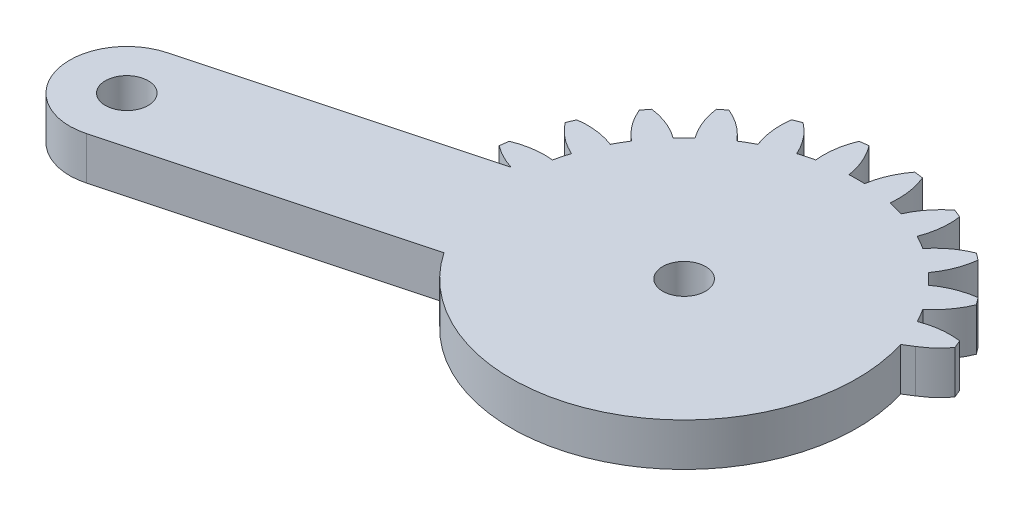
SolidWorks part; units mm, degrees
ref_plane "Front Plane" through (0, 0, 0) normal (0, 0, 1) x (1, 0, 0)
ref_plane "Top Plane" through (0, 0, 0) normal (0, 1, 0) x (1, 0, 0)
ref_plane "Right Plane" through (0, 0, 0) normal (1, 0, 0) x (0, 0, -1)
sketch "Sketch1" plane through (0, 0, 0) normal (0, 1, 0) x (1, 0, 0)
  line L0 (20.6437, 4) -> (2.0816, 4)
  line L1 (2.0816, -4) -> (20.6437, -4)
  arc A0 (2.0816, 4) -> (3.5217, 5.3071) centre (-0.7683, 8.5867) ccw
  arc A1 (3.5217, 5.3071) -> (3.2829, 5.8838) centre (-10.1063, 0) ccw
  arc A2 (3.2829, 5.8838) -> (0.6271, 5.5703) centre (2.5684, 0.5313) ccw
  arc A3 (0.6271, 5.5703) -> (0.0844, 6.5103) centre (-10.1063, 0) ccw
  arc A4 (0.0844, 6.5103) -> (1.6838, 8.6535) centre (-3.3089, 10.711) ccw
  arc A5 (1.6838, 8.6535) -> (1.3038, 9.1487) centre (-10.1063, 0) ccw
  arc A6 (1.3038, 9.1487) -> (-1.1803, 8.1585) centre (1.999, 3.7936) ccw
  arc A7 (-1.1803, 8.1585) -> (-1.9479, 8.926) centre (-10.1063, 0) ccw
  arc A8 (-1.9479, 8.926) -> (-0.9576, 11.4102) centre (-6.3127, 12.1053) ccw
  arc A9 (-0.9576, 11.4102) -> (-1.4528, 11.7901) centre (-10.1063, 0) ccw
  arc A10 (-1.4528, 11.7901) -> (-3.596, 10.1907) centre (0.6046, 6.7975) ccw
  arc A11 (-3.596, 10.1907) -> (-4.5361, 10.7334) centre (-10.1063, 0) ccw
  arc A12 (-4.5361, 10.7334) -> (-4.2225, 13.3892) centre (-9.5751, 12.6747) ccw
  arc A13 (-4.2225, 13.3892) -> (-4.7992, 13.6281) centre (-10.1063, 0) ccw
  arc A14 (-4.7992, 13.6281) -> (-6.4554, 11.5285) centre (-1.5196, 9.3381) ccw
  arc A15 (-6.4554, 11.5285) -> (-7.5039, 11.8094) centre (-10.1063, 0) ccw
  arc A16 (-7.5039, 11.8094) -> (-7.8884, 14.4558) centre (-12.8736, 12.3803) ccw
  arc A17 (-7.8884, 14.4558) -> (-8.5072, 14.5373) centre (-10.1063, 0) ccw
  arc A18 (-8.5072, 14.5373) -> (-9.5636, 12.0806) centre (-4.2291, 11.2423) ccw
  arc A19 (-9.5636, 12.0806) -> (-10.6491, 12.0806) centre (-10.1063, 0) ccw
  arc A20 (-10.6491, 12.0806) -> (-11.7054, 14.5373) centre (-15.9836, 11.2423) ccw
  arc A21 (-11.7054, 14.5373) -> (-12.3243, 14.4558) centre (-10.1063, 0) ccw
  arc A22 (-12.3243, 14.4558) -> (-12.7088, 11.8094) centre (-7.3391, 12.3803) ccw
  arc A23 (-12.7088, 11.8094) -> (-13.7573, 11.5285) centre (-10.1063, 0) ccw
  arc A24 (-13.7573, 11.5285) -> (-15.4135, 13.6281) centre (-18.6931, 9.3381) ccw
  arc A25 (-15.4135, 13.6281) -> (-15.9901, 13.3892) centre (-10.1063, 0) ccw
  arc A26 (-15.9901, 13.3892) -> (-15.6766, 10.7334) centre (-10.6376, 12.6747) ccw
  arc A27 (-15.6766, 10.7334) -> (-16.6166, 10.1907) centre (-10.1063, 0) ccw
  arc A28 (-16.6166, 10.1907) -> (-18.7599, 11.7901) centre (-20.8173, 6.7975) ccw
  arc A29 (-18.7599, 11.7901) -> (-19.255, 11.4102) centre (-10.1063, 0) ccw
  arc A30 (-19.255, 11.4102) -> (-18.2648, 8.926) centre (-13.9, 12.1053) ccw
  arc A31 (-18.2648, 8.926) -> (-19.0324, 8.1585) centre (-10.1063, 0) ccw
  arc A32 (-19.0324, 8.1585) -> (-21.5165, 9.1487) centre (-22.2117, 3.7936) ccw
  arc A33 (-21.5165, 9.1487) -> (-21.8965, 8.6535) centre (-10.1063, 0) ccw
  arc A34 (-21.8965, 8.6535) -> (-20.2971, 6.5103) centre (-16.9038, 10.711) ccw
  arc A35 (-20.2971, 6.5103) -> (-20.8398, 5.5703) centre (-10.1063, 0) ccw
  arc A36 (-20.8398, 5.5703) -> (-23.4956, 5.8838) centre (-22.7811, 0.5313) ccw
  arc A37 (-23.4956, 5.8838) -> (-23.7344, 5.3071) centre (-10.1063, 0) ccw
  arc A38 (-23.7344, 5.3071) -> (-21.6348, 3.6509) centre (-19.4444, 8.5867) ccw
  arc A39 (-21.6348, 3.6509) -> (-21.9157, 2.6025) centre (-10.1063, 0) ccw
  arc A40 (-21.9157, 2.6025) -> (-24.5622, 2.2179) centre (-22.4867, -2.7673) ccw
  arc A41 (-24.5622, 2.2179) -> (-24.6437, 1.5991) centre (-10.1063, 0) ccw
  arc A42 (-24.6437, 1.5991) -> (-22.1869, 0.5427) centre (-21.3486, 5.8773) ccw
  arc A43 (-22.1869, 0.5427) -> (-22.1869, -0.5427) centre (-10.1063, 0) ccw
  arc A44 (-22.1869, -0.5427) -> (-24.6437, -1.5991) centre (-21.3486, -5.8773) ccw
  arc A45 (-24.6437, -1.5991) -> (-24.5622, -2.2179) centre (-10.1063, 0) ccw
  arc A46 (-24.5622, -2.2179) -> (-21.9157, -2.6025) centre (-22.4867, 2.7673) ccw
  arc A47 (-21.9157, -2.6025) -> (-21.6348, -3.6509) centre (-10.1063, 0) ccw
  arc A48 (-21.6348, -3.6509) -> (-23.7344, -5.3071) centre (-19.4444, -8.5867) ccw
  arc A49 (-23.7344, -5.3071) -> (-23.4956, -5.8838) centre (-10.1063, 0) ccw
  arc A50 (-23.4956, -5.8838) -> (-20.8398, -5.5703) centre (-22.7811, -0.5313) ccw
  arc A51 (-20.8398, -5.5703) -> (-20.2971, -6.5103) centre (-10.1063, 0) ccw
  arc A52 (-20.2971, -6.5103) -> (-21.8965, -8.6535) centre (-16.9038, -10.711) ccw
  arc A53 (-21.8965, -8.6535) -> (-21.5165, -9.1487) centre (-10.1063, 0) ccw
  arc A54 (-21.5165, -9.1487) -> (-19.0324, -8.1585) centre (-22.2117, -3.7936) ccw
  arc A55 (-19.0324, -8.1585) -> (-18.2648, -8.926) centre (-10.1063, 0) ccw
  arc A56 (-18.2648, -8.926) -> (-19.255, -11.4102) centre (-13.9, -12.1053) ccw
  arc A57 (-19.255, -11.4102) -> (-18.7599, -11.7901) centre (-10.1063, 0) ccw
  arc A58 (-18.7599, -11.7901) -> (-16.6166, -10.1907) centre (-20.8173, -6.7975) ccw
  arc A59 (-16.6166, -10.1907) -> (-15.6766, -10.7334) centre (-10.1063, 0) ccw
  arc A60 (-15.6766, -10.7334) -> (-15.9901, -13.3892) centre (-10.6376, -12.6747) ccw
  arc A61 (-15.9901, -13.3892) -> (-15.4135, -13.6281) centre (-10.1063, 0) ccw
  arc A62 (-15.4135, -13.6281) -> (-13.7573, -11.5285) centre (-18.6931, -9.3381) ccw
  arc A63 (-13.7573, -11.5285) -> (-12.7088, -11.8094) centre (-10.1063, 0) ccw
  arc A64 (-12.7088, -11.8094) -> (-12.3243, -14.4558) centre (-7.3391, -12.3803) ccw
  arc A65 (-12.3243, -14.4558) -> (-11.7054, -14.5373) centre (-10.1063, 0) ccw
  arc A66 (-11.7054, -14.5373) -> (-10.6491, -12.0806) centre (-15.9836, -11.2423) ccw
  arc A67 (-10.6491, -12.0806) -> (-9.5636, -12.0806) centre (-10.1063, 0) ccw
  arc A68 (-9.5636, -12.0806) -> (-8.5072, -14.5373) centre (-4.2291, -11.2423) ccw
  arc A69 (-8.5072, -14.5373) -> (-7.8884, -14.4558) centre (-10.1063, 0) ccw
  arc A70 (-7.8884, -14.4558) -> (-7.5039, -11.8094) centre (-12.8736, -12.3803) ccw
  arc A71 (-7.5039, -11.8094) -> (-6.4554, -11.5285) centre (-10.1063, 0) ccw
  arc A72 (-6.4554, -11.5285) -> (-4.7992, -13.6281) centre (-1.5196, -9.3381) ccw
  arc A73 (-4.7992, -13.6281) -> (-4.2225, -13.3892) centre (-10.1063, 0) ccw
  arc A74 (-4.2225, -13.3892) -> (-4.5361, -10.7334) centre (-9.5751, -12.6747) ccw
  arc A75 (-4.5361, -10.7334) -> (-3.596, -10.1907) centre (-10.1063, 0) ccw
  arc A76 (-3.596, -10.1907) -> (-1.4528, -11.7901) centre (0.6046, -6.7975) ccw
  arc A77 (-1.4528, -11.7901) -> (-0.9576, -11.4102) centre (-10.1063, 0) ccw
  arc A78 (-0.9576, -11.4102) -> (-1.9479, -8.926) centre (-6.3127, -12.1053) ccw
  arc A79 (-1.9479, -8.926) -> (-1.1803, -8.1585) centre (-10.1063, 0) ccw
  arc A80 (-1.1803, -8.1585) -> (1.3038, -9.1487) centre (1.999, -3.7936) ccw
  arc A81 (1.3038, -9.1487) -> (1.6838, -8.6535) centre (-10.1063, 0) ccw
  arc A82 (1.6838, -8.6535) -> (0.0844, -6.5103) centre (-3.3089, -10.711) ccw
  arc A83 (0.0844, -6.5103) -> (0.6271, -5.5703) centre (-10.1063, 0) ccw
  arc A84 (0.6271, -5.5703) -> (3.2829, -5.8838) centre (2.5684, -0.5313) ccw
  arc A85 (3.2829, -5.8838) -> (3.5217, -5.3071) centre (-10.1063, 0) ccw
  arc A86 (3.5217, -5.3071) -> (2.0816, -4) centre (-0.7683, -8.5867) ccw
  arc A87 (20.6437, -4) -> (20.6437, 4) centre (20.6437, 0) ccw
  circle A88 centre (-10.1063, 0) radius 1.5
  circle A89 centre (20.6437, 0) radius 1.5
  dimension "D1" = 3
  dimension "D2" = 3
extrude "Boss-Extrude1" add sketch "Sketch1" along normal blind 3
sketch "Sketch3" plane through (0, 3, 0) normal (0, 1, 0) x (1, 0, 0)
  line L0 (-10.1063, 0) -> (-40.8563, 0) construction
  line L1 (-10.1063, 0) -> (-40.8563, -8.2394)
  line L2 (-11.1416, 3.8637) -> (-41.8916, -4.3757)
  line L3 (-9.0711, -3.8637) -> (-39.8211, -12.1031)
  circle A0 centre (-10.1063, 0) radius 1.5
  circle A1 centre (20.6437, 0) radius 1.5 construction
  circle A2 centre (20.6437, 0) radius 1.5
  circle A3 centre (-40.8563, -8.2394) radius 1.5
  circle A4 centre (-40.8563, -8.2394) radius 4
  circle A5 centre (-10.1063, 0) radius 4
  dimension "D2" = 3
  dimension "D5" = 3
  dimension "D6" = 8
  dimension "D7" = 8
  dimension "D1" = 30.75
  dimension "D3" = 30.75
  dimension "D4" = 15
extrude "Boss-Extrude2" add sketch "Sketch3" against normal blind 3 contours L0 A5 L2 | A5 L0 L2 A4 L1 | A4 A3 | A5 L1 A4 L3 | L0 A0 L1 A5 | A0 L0 A5 L1 region at (-13.0123, 3, 0.3826) region at (-12.8563, 3, -0.1131) region at (-28.0097, 3, 2.8847) region at (-17.5095, 3, -1.168) region at (-24.9445, 3, 6.1234) region at (-37.0027, 3, 7.7321)
sketch "Sketch4" plane through (0, 3, 0) normal (0, 1, 0) x (1, 0, 0)
  line L0 (20.6437, 4) -> (2.0816, 4) construction
  line L1 (2.0816, -4) -> (20.6437, -4) construction
  line L2 (20.6437, 4) -> (2.0816, 4)
  line L3 (2.0816, -4) -> (20.6437, -4)
  line L4 (2.0816, 4) -> (1.4381, 3.6001)
  line L5 (-20.8438, -7.0182) -> (-20.0942, -6.8174)
  line L8 (-22.9143, 0.7092) -> (-41.8916, -4.3757)
  line L9 (-39.8211, -12.1031) -> (-20.8438, -7.0182)
  line L10 (2.0816, -4) -> (20.6437, -4)
  line L11 (20.6437, 4) -> (2.0816, 4)
  line L12 (-22.9143, 0.7092) -> (-41.8916, -4.3757)
  line L13 (-39.8211, -12.1031) -> (-20.8438, -7.0182)
  line L14 (2.0816, -4) -> (20.6437, -4)
  line L15 (20.6437, 4) -> (2.0816, 4)
  circle A0 centre (-10.1063, 0) radius 12.0927
  arc A1 (3.2829, 5.8838) -> (0.6271, 5.5703) centre (2.5684, 0.5313) ccw construction
  arc A2 (3.5217, 5.3071) -> (3.2829, 5.8838) centre (-10.1063, 0) ccw construction
  arc A3 (2.0816, 4) -> (3.5217, 5.3071) centre (-0.7683, 8.5867) ccw construction
  arc A4 (20.6437, -4) -> (20.6437, 4) centre (20.6437, 0) ccw construction
  arc A5 (3.5217, -5.3071) -> (2.0816, -4) centre (-0.7683, -8.5867) ccw construction
  arc A6 (3.2829, -5.8838) -> (3.5217, -5.3071) centre (-10.1063, 0) ccw construction
  arc A7 (0.6271, -5.5703) -> (3.2829, -5.8838) centre (2.5684, -0.5313) ccw construction
  arc A8 (3.2829, 5.8838) -> (0.6271, 5.5703) centre (2.5684, 0.5313) ccw
  arc A9 (3.5217, 5.3071) -> (3.2829, 5.8838) centre (-10.1063, 0) ccw
  arc A10 (2.0816, 4) -> (3.5217, 5.3071) centre (-0.7683, 8.5867) ccw
  arc A11 (20.6437, -4) -> (20.6437, 4) centre (20.6437, 0) ccw
  arc A12 (3.5217, -5.3071) -> (2.0816, -4) centre (-0.7683, -8.5867) ccw
  arc A13 (3.2829, -5.8838) -> (3.5217, -5.3071) centre (-10.1063, 0) ccw
  arc A14 (0.6271, -5.5703) -> (3.2829, -5.8838) centre (2.5684, -0.5313) ccw
  arc A95 (-24.6437, 1.5991) -> (-22.9143, 0.7092) centre (-21.3486, 5.8773) ccw
  arc A96 (-41.8916, -4.3757) -> (-39.8211, -12.1031) centre (-40.8563, -8.2394) ccw
  arc A97 (-20.8438, -7.0182) -> (-21.8965, -8.6535) centre (-16.9038, -10.711) ccw
  arc A98 (-21.8965, -8.6535) -> (-21.5165, -9.1487) centre (-10.1063, 0) ccw
  arc A99 (-21.5165, -9.1487) -> (-19.0324, -8.1585) centre (-22.2117, -3.7936) ccw
  arc A100 (-19.0324, -8.1585) -> (-18.2648, -8.926) centre (-10.1063, 0) ccw
  arc A101 (-18.2648, -8.926) -> (-19.255, -11.4102) centre (-13.9, -12.1053) ccw
  arc A102 (-19.255, -11.4102) -> (-18.7599, -11.7901) centre (-10.1063, 0) ccw
  arc A103 (-18.7599, -11.7901) -> (-16.6166, -10.1907) centre (-20.8173, -6.7975) ccw
  arc A104 (-16.6166, -10.1907) -> (-15.6766, -10.7334) centre (-10.1063, 0) ccw
  arc A105 (-15.6766, -10.7334) -> (-15.9901, -13.3892) centre (-10.6376, -12.6747) ccw
  arc A106 (-15.9901, -13.3892) -> (-15.4135, -13.6281) centre (-10.1063, 0) ccw
  arc A107 (-15.4135, -13.6281) -> (-13.7573, -11.5285) centre (-18.6931, -9.3381) ccw
  arc A108 (-13.7573, -11.5285) -> (-12.7088, -11.8094) centre (-10.1063, 0) ccw
  arc A109 (-12.7088, -11.8094) -> (-12.3243, -14.4558) centre (-7.3391, -12.3803) ccw
  arc A110 (-12.3243, -14.4558) -> (-11.7054, -14.5373) centre (-10.1063, 0) ccw
  arc A111 (-11.7054, -14.5373) -> (-10.6491, -12.0806) centre (-15.9836, -11.2423) ccw
  arc A112 (-10.6491, -12.0806) -> (-9.5636, -12.0806) centre (-10.1063, 0) ccw
  arc A113 (-9.5636, -12.0806) -> (-8.5072, -14.5373) centre (-4.2291, -11.2423) ccw
  arc A114 (-8.5072, -14.5373) -> (-7.8884, -14.4558) centre (-10.1063, 0) ccw
  arc A115 (-7.8884, -14.4558) -> (-7.5039, -11.8094) centre (-12.8736, -12.3803) ccw
  arc A116 (-7.5039, -11.8094) -> (-6.4554, -11.5285) centre (-10.1063, 0) ccw
  arc A117 (-6.4554, -11.5285) -> (-4.7992, -13.6281) centre (-1.5196, -9.3381) ccw
  arc A118 (-4.7992, -13.6281) -> (-4.2225, -13.3892) centre (-10.1063, 0) ccw
  arc A119 (-4.2225, -13.3892) -> (-4.5361, -10.7334) centre (-9.5751, -12.6747) ccw
  arc A120 (-4.5361, -10.7334) -> (-3.596, -10.1907) centre (-10.1063, 0) ccw
  arc A121 (-3.596, -10.1907) -> (-1.4528, -11.7901) centre (0.6046, -6.7975) ccw
  arc A122 (-1.4528, -11.7901) -> (-0.9576, -11.4102) centre (-10.1063, 0) ccw
  arc A123 (-0.9576, -11.4102) -> (-1.9479, -8.926) centre (-6.3127, -12.1053) ccw
  arc A124 (-1.9479, -8.926) -> (-1.1803, -8.1585) centre (-10.1063, 0) ccw
  arc A125 (-1.1803, -8.1585) -> (1.3038, -9.1487) centre (1.999, -3.7936) ccw
  arc A126 (1.3038, -9.1487) -> (1.6838, -8.6535) centre (-10.1063, 0) ccw
  arc A127 (1.6838, -8.6535) -> (0.0844, -6.5103) centre (-3.3089, -10.711) ccw
  arc A128 (0.0844, -6.5103) -> (0.6271, -5.5703) centre (-10.1063, 0) ccw
  arc A129 (0.6271, -5.5703) -> (3.2829, -5.8838) centre (2.5684, -0.5313) ccw
  arc A130 (3.2829, -5.8838) -> (3.5217, -5.3071) centre (-10.1063, 0) ccw
  arc A131 (3.5217, -5.3071) -> (2.0816, -4) centre (-0.7683, -8.5867) ccw
  arc A132 (20.6437, -4) -> (20.6437, 4) centre (20.6437, 0) ccw
  arc A133 (2.0816, 4) -> (3.5217, 5.3071) centre (-0.7683, 8.5867) ccw
  arc A134 (3.5217, 5.3071) -> (3.2829, 5.8838) centre (-10.1063, 0) ccw
  arc A135 (3.2829, 5.8838) -> (0.6271, 5.5703) centre (2.5684, 0.5313) ccw
  arc A136 (0.6271, 5.5703) -> (0.0844, 6.5103) centre (-10.1063, 0) ccw
  arc A137 (0.0844, 6.5103) -> (1.6838, 8.6535) centre (-3.3089, 10.711) ccw
  arc A138 (1.6838, 8.6535) -> (1.3038, 9.1487) centre (-10.1063, 0) ccw
  arc A139 (1.3038, 9.1487) -> (-1.1803, 8.1585) centre (1.999, 3.7936) ccw
  arc A140 (-1.1803, 8.1585) -> (-1.9479, 8.926) centre (-10.1063, 0) ccw
  arc A141 (-1.9479, 8.926) -> (-0.9576, 11.4102) centre (-6.3127, 12.1053) ccw
  arc A142 (-0.9576, 11.4102) -> (-1.4528, 11.7901) centre (-10.1063, 0) ccw
  arc A143 (-1.4528, 11.7901) -> (-3.596, 10.1907) centre (0.6046, 6.7975) ccw
  arc A144 (-3.596, 10.1907) -> (-4.5361, 10.7334) centre (-10.1063, 0) ccw
  arc A145 (-4.5361, 10.7334) -> (-4.2225, 13.3892) centre (-9.5751, 12.6747) ccw
  arc A146 (-4.2225, 13.3892) -> (-4.7992, 13.6281) centre (-10.1063, 0) ccw
  arc A147 (-4.7992, 13.6281) -> (-6.4554, 11.5285) centre (-1.5196, 9.3381) ccw
  arc A148 (-6.4554, 11.5285) -> (-7.5039, 11.8094) centre (-10.1063, 0) ccw
  arc A149 (-7.5039, 11.8094) -> (-7.8884, 14.4558) centre (-12.8736, 12.3803) ccw
  arc A150 (-7.8884, 14.4558) -> (-8.5072, 14.5373) centre (-10.1063, 0) ccw
  arc A151 (-8.5072, 14.5373) -> (-9.5636, 12.0806) centre (-4.2291, 11.2423) ccw
  arc A152 (-9.5636, 12.0806) -> (-10.6491, 12.0806) centre (-10.1063, 0) ccw
  arc A153 (-10.6491, 12.0806) -> (-11.7054, 14.5373) centre (-15.9836, 11.2423) ccw
  arc A154 (-11.7054, 14.5373) -> (-12.3243, 14.4558) centre (-10.1063, 0) ccw
  arc A155 (-12.3243, 14.4558) -> (-12.7088, 11.8094) centre (-7.3391, 12.3803) ccw
  arc A156 (-12.7088, 11.8094) -> (-13.7573, 11.5285) centre (-10.1063, 0) ccw
  arc A157 (-13.7573, 11.5285) -> (-15.4135, 13.6281) centre (-18.6931, 9.3381) ccw
  arc A158 (-15.4135, 13.6281) -> (-15.9901, 13.3892) centre (-10.1063, 0) ccw
  arc A159 (-15.9901, 13.3892) -> (-15.6766, 10.7334) centre (-10.6376, 12.6747) ccw
  arc A160 (-15.6766, 10.7334) -> (-16.6166, 10.1907) centre (-10.1063, 0) ccw
  arc A161 (-16.6166, 10.1907) -> (-18.7599, 11.7901) centre (-20.8173, 6.7975) ccw
  arc A162 (-18.7599, 11.7901) -> (-19.255, 11.4102) centre (-10.1063, 0) ccw
  arc A163 (-19.255, 11.4102) -> (-18.2648, 8.926) centre (-13.9, 12.1053) ccw
  arc A164 (-18.2648, 8.926) -> (-19.0324, 8.1585) centre (-10.1063, 0) ccw
  arc A165 (-19.0324, 8.1585) -> (-21.5165, 9.1487) centre (-22.2117, 3.7936) ccw
  arc A166 (-21.5165, 9.1487) -> (-21.8965, 8.6535) centre (-10.1063, 0) ccw
  arc A167 (-21.8965, 8.6535) -> (-20.2971, 6.5103) centre (-16.9038, 10.711) ccw
  arc A168 (-20.2971, 6.5103) -> (-20.8398, 5.5703) centre (-10.1063, 0) ccw
  arc A169 (-20.8398, 5.5703) -> (-23.4956, 5.8838) centre (-22.7811, 0.5313) ccw
  arc A170 (-23.4956, 5.8838) -> (-23.7344, 5.3071) centre (-10.1063, 0) ccw
  arc A171 (-23.7344, 5.3071) -> (-21.6348, 3.6509) centre (-19.4444, 8.5867) ccw
  arc A172 (-21.6348, 3.6509) -> (-21.9157, 2.6025) centre (-10.1063, 0) ccw
  arc A173 (-21.9157, 2.6025) -> (-24.5622, 2.2179) centre (-22.4867, -2.7673) ccw
  arc A174 (-24.5622, 2.2179) -> (-24.6437, 1.5991) centre (-10.1063, 0) ccw
  arc A175 (-24.6437, 1.5991) -> (-22.9143, 0.7092) centre (-21.3486, 5.8773) ccw
  arc A176 (-41.8916, -4.3757) -> (-39.8211, -12.1031) centre (-40.8563, -8.2394) ccw
  arc A177 (-20.8438, -7.0182) -> (-21.8965, -8.6535) centre (-16.9038, -10.711) ccw
  arc A178 (-21.8965, -8.6535) -> (-21.5165, -9.1487) centre (-10.1063, 0) ccw
  arc A179 (-21.5165, -9.1487) -> (-19.0324, -8.1585) centre (-22.2117, -3.7936) ccw
  arc A180 (-19.0324, -8.1585) -> (-18.2648, -8.926) centre (-10.1063, 0) ccw
  arc A181 (-18.2648, -8.926) -> (-19.255, -11.4102) centre (-13.9, -12.1053) ccw
  arc A182 (-19.255, -11.4102) -> (-18.7599, -11.7901) centre (-10.1063, 0) ccw
  arc A183 (-18.7599, -11.7901) -> (-16.6166, -10.1907) centre (-20.8173, -6.7975) ccw
  arc A184 (-16.6166, -10.1907) -> (-15.6766, -10.7334) centre (-10.1063, 0) ccw
  arc A185 (-15.6766, -10.7334) -> (-15.9901, -13.3892) centre (-10.6376, -12.6747) ccw
  arc A186 (-15.9901, -13.3892) -> (-15.4135, -13.6281) centre (-10.1063, 0) ccw
  arc A187 (-15.4135, -13.6281) -> (-13.7573, -11.5285) centre (-18.6931, -9.3381) ccw
  arc A188 (-13.7573, -11.5285) -> (-12.7088, -11.8094) centre (-10.1063, 0) ccw
  arc A189 (-12.7088, -11.8094) -> (-12.3243, -14.4558) centre (-7.3391, -12.3803) ccw
  arc A190 (-12.3243, -14.4558) -> (-11.7054, -14.5373) centre (-10.1063, 0) ccw
  arc A191 (-11.7054, -14.5373) -> (-10.6491, -12.0806) centre (-15.9836, -11.2423) ccw
  arc A192 (-10.6491, -12.0806) -> (-9.5636, -12.0806) centre (-10.1063, 0) ccw
  arc A193 (-9.5636, -12.0806) -> (-8.5072, -14.5373) centre (-4.2291, -11.2423) ccw
  arc A194 (-8.5072, -14.5373) -> (-7.8884, -14.4558) centre (-10.1063, 0) ccw
  arc A195 (-7.8884, -14.4558) -> (-7.5039, -11.8094) centre (-12.8736, -12.3803) ccw
  arc A196 (-7.5039, -11.8094) -> (-6.4554, -11.5285) centre (-10.1063, 0) ccw
  arc A197 (-6.4554, -11.5285) -> (-4.7992, -13.6281) centre (-1.5196, -9.3381) ccw
  arc A198 (-4.7992, -13.6281) -> (-4.2225, -13.3892) centre (-10.1063, 0) ccw
  arc A199 (-4.2225, -13.3892) -> (-4.5361, -10.7334) centre (-9.5751, -12.6747) ccw
  arc A200 (-4.5361, -10.7334) -> (-3.596, -10.1907) centre (-10.1063, 0) ccw
  arc A201 (-3.596, -10.1907) -> (-1.4528, -11.7901) centre (0.6046, -6.7975) ccw
  arc A202 (-1.4528, -11.7901) -> (-0.9576, -11.4102) centre (-10.1063, 0) ccw
  arc A203 (-0.9576, -11.4102) -> (-1.9479, -8.926) centre (-6.3127, -12.1053) ccw
  arc A204 (-1.9479, -8.926) -> (-1.1803, -8.1585) centre (-10.1063, 0) ccw
  arc A205 (-1.1803, -8.1585) -> (1.3038, -9.1487) centre (1.999, -3.7936) ccw
  arc A206 (1.3038, -9.1487) -> (1.6838, -8.6535) centre (-10.1063, 0) ccw
  arc A207 (1.6838, -8.6535) -> (0.0844, -6.5103) centre (-3.3089, -10.711) ccw
  arc A208 (0.0844, -6.5103) -> (0.6271, -5.5703) centre (-10.1063, 0) ccw
  arc A209 (0.6271, -5.5703) -> (3.2829, -5.8838) centre (2.5684, -0.5313) ccw
  arc A210 (3.2829, -5.8838) -> (3.5217, -5.3071) centre (-10.1063, 0) ccw
  arc A211 (3.5217, -5.3071) -> (2.0816, -4) centre (-0.7683, -8.5867) ccw
  arc A212 (20.6437, -4) -> (20.6437, 4) centre (20.6437, 0) ccw
  arc A213 (2.0816, 4) -> (3.5217, 5.3071) centre (-0.7683, 8.5867) ccw
  arc A214 (3.5217, 5.3071) -> (3.2829, 5.8838) centre (-10.1063, 0) ccw
  arc A215 (3.2829, 5.8838) -> (0.6271, 5.5703) centre (2.5684, 0.5313) ccw
  arc A216 (0.6271, 5.5703) -> (0.0844, 6.5103) centre (-10.1063, 0) ccw
  arc A217 (0.0844, 6.5103) -> (1.6838, 8.6535) centre (-3.3089, 10.711) ccw
  arc A218 (1.6838, 8.6535) -> (1.3038, 9.1487) centre (-10.1063, 0) ccw
  arc A219 (1.3038, 9.1487) -> (-1.1803, 8.1585) centre (1.999, 3.7936) ccw
  arc A220 (-1.1803, 8.1585) -> (-1.9479, 8.926) centre (-10.1063, 0) ccw
  arc A221 (-1.9479, 8.926) -> (-0.9576, 11.4102) centre (-6.3127, 12.1053) ccw
  arc A222 (-0.9576, 11.4102) -> (-1.4528, 11.7901) centre (-10.1063, 0) ccw
  arc A223 (-1.4528, 11.7901) -> (-3.596, 10.1907) centre (0.6046, 6.7975) ccw
  arc A224 (-3.596, 10.1907) -> (-4.5361, 10.7334) centre (-10.1063, 0) ccw
  arc A225 (-4.5361, 10.7334) -> (-4.2225, 13.3892) centre (-9.5751, 12.6747) ccw
  arc A226 (-4.2225, 13.3892) -> (-4.7992, 13.6281) centre (-10.1063, 0) ccw
  arc A227 (-4.7992, 13.6281) -> (-6.4554, 11.5285) centre (-1.5196, 9.3381) ccw
  arc A228 (-6.4554, 11.5285) -> (-7.5039, 11.8094) centre (-10.1063, 0) ccw
  arc A229 (-7.5039, 11.8094) -> (-7.8884, 14.4558) centre (-12.8736, 12.3803) ccw
  arc A230 (-7.8884, 14.4558) -> (-8.5072, 14.5373) centre (-10.1063, 0) ccw
  arc A231 (-8.5072, 14.5373) -> (-9.5636, 12.0806) centre (-4.2291, 11.2423) ccw
  arc A232 (-9.5636, 12.0806) -> (-10.6491, 12.0806) centre (-10.1063, 0) ccw
  arc A233 (-10.6491, 12.0806) -> (-11.7054, 14.5373) centre (-15.9836, 11.2423) ccw
  arc A234 (-11.7054, 14.5373) -> (-12.3243, 14.4558) centre (-10.1063, 0) ccw
  arc A235 (-12.3243, 14.4558) -> (-12.7088, 11.8094) centre (-7.3391, 12.3803) ccw
  arc A236 (-12.7088, 11.8094) -> (-13.7573, 11.5285) centre (-10.1063, 0) ccw
  arc A237 (-13.7573, 11.5285) -> (-15.4135, 13.6281) centre (-18.6931, 9.3381) ccw
  arc A238 (-15.4135, 13.6281) -> (-15.9901, 13.3892) centre (-10.1063, 0) ccw
  arc A239 (-15.9901, 13.3892) -> (-15.6766, 10.7334) centre (-10.6376, 12.6747) ccw
  arc A240 (-15.6766, 10.7334) -> (-16.6166, 10.1907) centre (-10.1063, 0) ccw
  arc A241 (-16.6166, 10.1907) -> (-18.7599, 11.7901) centre (-20.8173, 6.7975) ccw
  arc A242 (-18.7599, 11.7901) -> (-19.255, 11.4102) centre (-10.1063, 0) ccw
  arc A243 (-19.255, 11.4102) -> (-18.2648, 8.926) centre (-13.9, 12.1053) ccw
  arc A244 (-18.2648, 8.926) -> (-19.0324, 8.1585) centre (-10.1063, 0) ccw
  arc A245 (-19.0324, 8.1585) -> (-21.5165, 9.1487) centre (-22.2117, 3.7936) ccw
  arc A246 (-21.5165, 9.1487) -> (-21.8965, 8.6535) centre (-10.1063, 0) ccw
  arc A247 (-21.8965, 8.6535) -> (-20.2971, 6.5103) centre (-16.9038, 10.711) ccw
  arc A248 (-20.2971, 6.5103) -> (-20.8398, 5.5703) centre (-10.1063, 0) ccw
  arc A249 (-20.8398, 5.5703) -> (-23.4956, 5.8838) centre (-22.7811, 0.5313) ccw
  arc A250 (-23.4956, 5.8838) -> (-23.7344, 5.3071) centre (-10.1063, 0) ccw
  arc A251 (-23.7344, 5.3071) -> (-21.6348, 3.6509) centre (-19.4444, 8.5867) ccw
  arc A252 (-21.6348, 3.6509) -> (-21.9157, 2.6025) centre (-10.1063, 0) ccw
  arc A253 (-21.9157, 2.6025) -> (-24.5622, 2.2179) centre (-22.4867, -2.7673) ccw
  arc A254 (-24.5622, 2.2179) -> (-24.6437, 1.5991) centre (-10.1063, 0) ccw
  dimension "D2" = 24.1855
  dimension "D1" = 0
extrude "Cut-Extrude1" cut sketch "Sketch4" against normal blind 3 contours A178 A179 A0 L5 A177 | A182 A183 A0 A181 | A186 A187 A0 A185 | A190 A191 A0 A189 | A194 A195 A0 A193 | A198 A199 A0 A197 | A202 A203 A0 A201 | A206 A207 A0 A205 | A0 A14 A13 A12 L3 A11 L2 L4 region at (12.5694, 3, 0.1127) region at (0.3325, 3, 8.01) region at (-2.0963, 3, 10.4389) region at (-5.071, 3, 12.1563) region at (-8.3889, 3, 13.0454) region at (-11.8238, 3, 13.0454) region at (-15.1417, 3, 12.1563) region at (-18.1164, 3, 10.4389) region at (-20.5498, 3, 8.0549)
